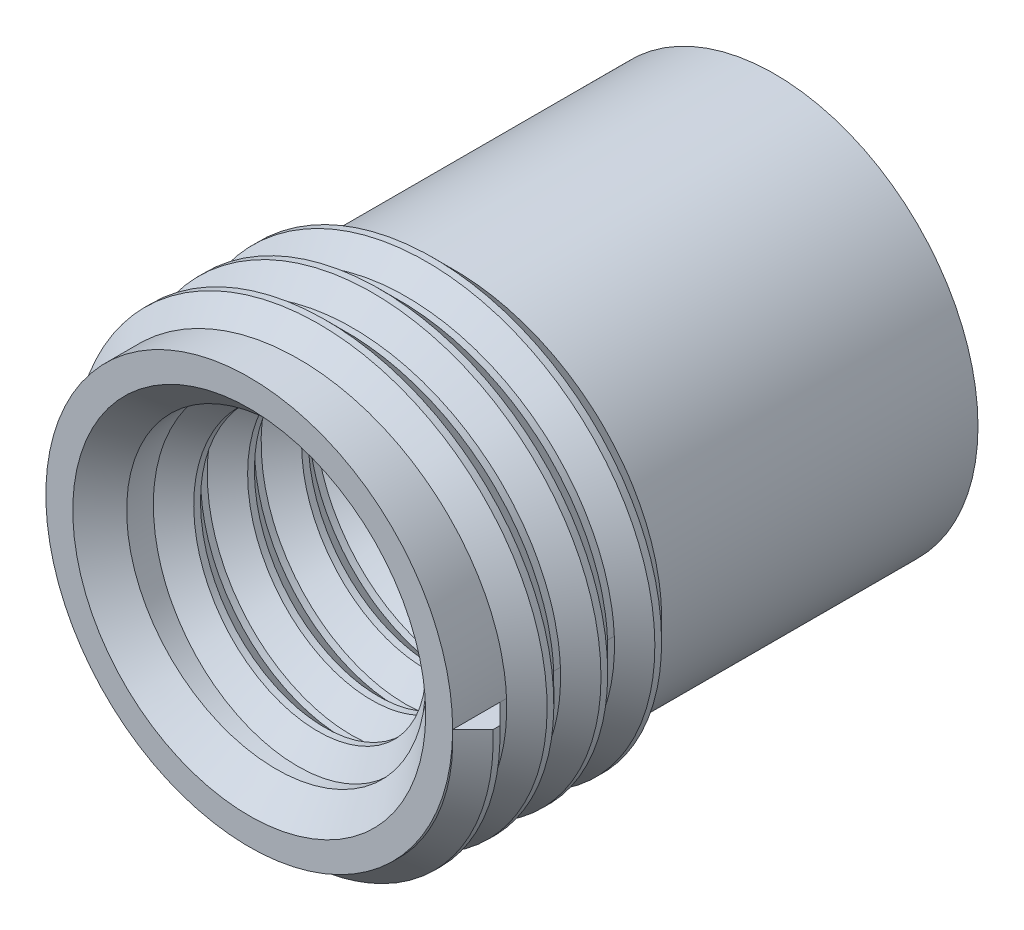
SolidWorks part; units mm, degrees
ref_plane "前视基准面" through (0, 0, 0) normal (0, 0, 1) x (1, 0, 0)
ref_plane "上视基准面" through (0, 0, 0) normal (0, 1, 0) x (1, 0, 0)
ref_plane "右视基准面" through (0, 0, 0) normal (1, 0, 0) x (0, 0, -1)
sketch "草图1" plane through (0, 0, 0) normal (0, 0, 1) x (1, 0, 0)
  circle A0 centre (0, 0) radius 15.1
  dimension "D1" = 30.2
extrude "凸台-拉伸1" add sketch "草图1" along normal blind 39 contours A0
ref_plane "基准面1" through (0, 0, 37.25) normal (0, 0, 1) x (1, 0, 0)
sketch "草图2" plane through (0, 0, 37.25) normal (0, 0, 1) x (1, 0, 0)
  circle A0 centre (0, 0) radius 15.1 construction
  circle A1 centre (0, 0) radius 15.1
curve "螺旋线/涡状线1" pitch 4 height 14 radius 15.1 centre (0, 0, 37.25) axis (0, 0, -1) start towards (1, 0, 0)
sketch "草图3" plane through (0, 0, 0) normal (0, 1, 0) x (1, 0, 0)
  line L0 (15.1, -35.5) -> (15.1, -39)
  line L1 (15.1, -39) -> (16.6, -37.5)
  line L2 (16.6, -37.5) -> (16.6, -37)
  line L3 (16.6, -37) -> (15.1, -35.5)
  point P2 (15.1, -37.25)
  dimension "D1" = 3.5
  dimension "D3" = 45
  dimension "D4" = 1.5
sweep "扫描1" add profiles "草图3" path "螺旋线/涡状线1"
sketch "草图4" plane through (0, 0, 39) normal (0, 0, 1) x (1, 0, 0)
  circle A0 centre (0, 0) radius 11.1
  circle A1 centre (0, 0) radius 15.1 construction
  dimension "D1" = 4
extrude "中孔" cut sketch "草图4" against normal through all contours A0
sketch "草图8" plane through (0, 0, 0) normal (0, 1, 0) x (1, 0, 0)
  line L0 (-11.1, 0) -> (-11.1, -39) construction
  line L1 (-11.1, -37) -> (-11.1, -39)
  line L4 (-11.1, -37) -> (-13.1, -39)
  line L5 (-15.1, -39) -> (15.1, -39) construction
  line L6 (-13.1, -39) -> (-11.1, -39)
  line L7 (0, 0) -> (0, 50000) construction
  dimension "D1" = 2
  dimension "D2" = 2
revolve "切除-旋转1" cut sketch "草图8" angle 360 about L7
ref_plane "基准面3" through (0, 0, 35.25) normal (0, 0, 1) x (1, 0, 0)
sketch "草图9" plane through (0, 0, 35.25) normal (0, 0, 1) x (1, 0, 0)
  circle A0 centre (0, 0) radius 11.1 construction
  circle A1 centre (0, 0) radius 11.1
curve "螺旋线/涡状线2" pitch 4 height 14 radius 11.1 centre (0, 0, 35.25) axis (0, 0, -1) start towards (1, 0, 0)
sketch "草图10" plane through (0, 0, 0) normal (0, 1, 0) x (1, 0, 0)
  line L0 (11.1, -33.5) -> (11.1, -37)
  line L1 (11.1, -37) -> (9.6, -35.5)
  line L2 (9.6, -35.5) -> (9.6, -35)
  line L3 (9.6, -35) -> (11.1, -33.5)
  point P4 (11.1, -35.25)
  dimension "D1" = 3.5
  dimension "D2" = 1.5
  dimension "D3" = 45
sweep "扫描2" add profiles "草图10" path "螺旋线/涡状线2"
ref_plane "基准面4" through (0, 0, 24) normal (0, 0, 1) x (1, 0, 0)
